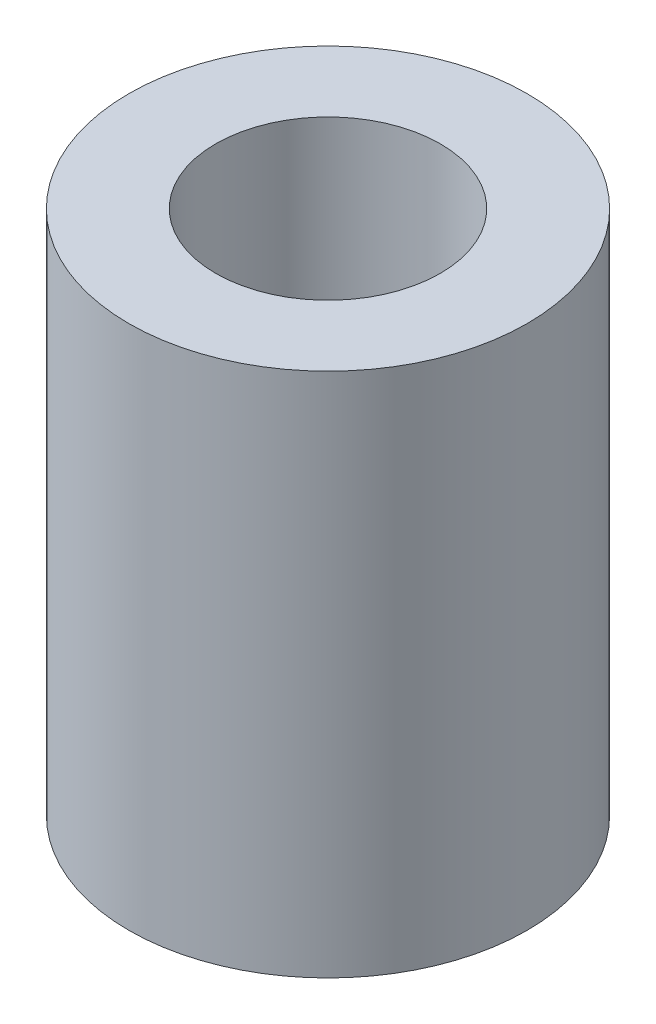
SolidWorks part; units mm, degrees
ref_plane "Front Plane" through (0, 0, 0) normal (0, 0, 1) x (1, 0, 0)
ref_plane "Top Plane" through (0, 0, 0) normal (0, 1, 0) x (1, 0, 0)
ref_plane "Right Plane" through (0, 0, 0) normal (1, 0, 0) x (0, 0, -1)
sketch "Sketch1" plane through (0, 0, 0) normal (0, 1, 0) x (1, 0, 0)
  circle A0 centre (0, 0) radius 5
  dimension "SLEEVE_OD" = 10
extrude "Boss-Extrude1" add sketch "Sketch1" along normal blind 13.1938
sketch "Sketch2" plane through (0, 0, 0) normal (0, 1, 0) x (1, 0, 0)
  circle A0 centre (0, 0) radius 2.8191
  dimension "BORE_D" = 5.6381
extrude "Cut-Extrude1" cut sketch "Sketch2" along normal through all
chamfer "Chamfer1" distance 0.7694 angle 66.571 rebuild error yes
